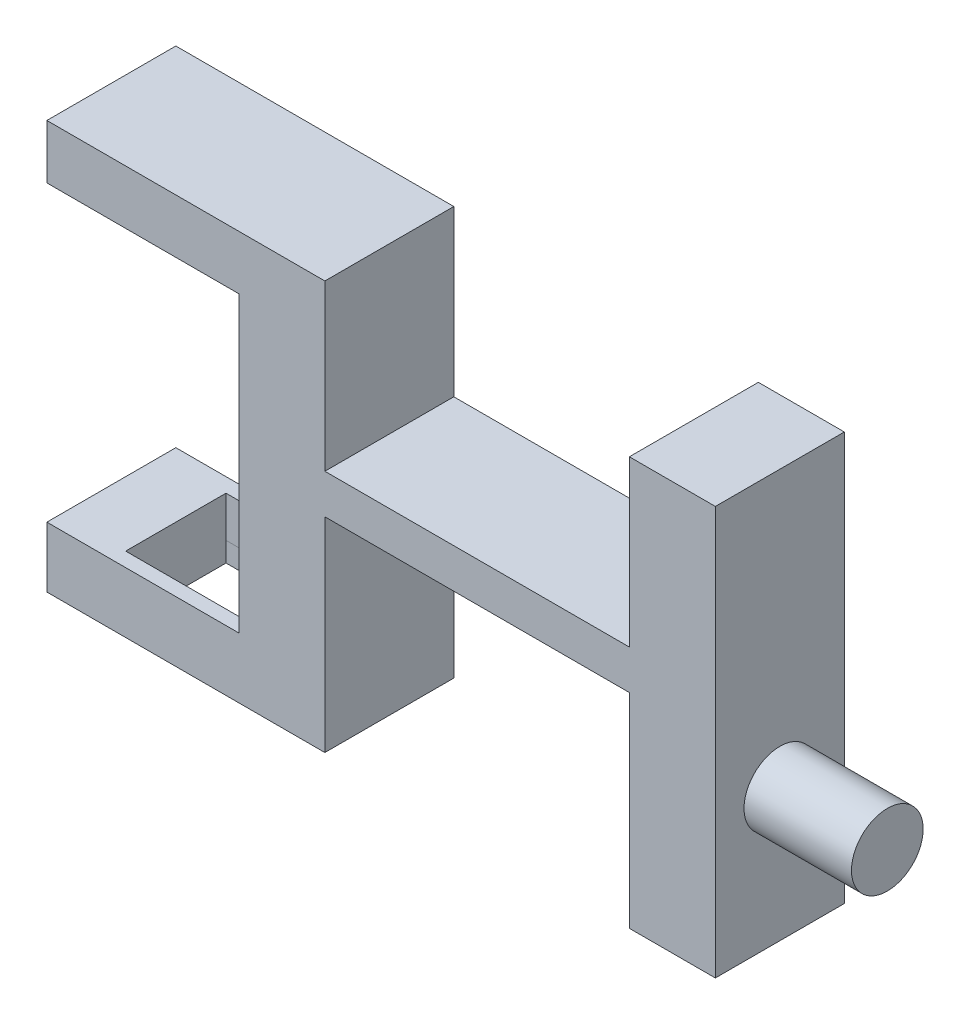
SolidWorks part; units mm, degrees
material "PLA"
ref_plane "Front Plane" through (0, 0, 0) normal (0, 0, 1) x (1, 0, 0)
ref_plane "Top Plane" through (0, 0, 0) normal (0, 1, 0) x (1, 0, 0)
ref_plane "Right Plane" through (0, 0, 0) normal (1, 0, 0) x (0, 0, -1)
sketch "Sketch2" plane through (0, 0, 0) normal (0, 0, 1) x (1, 0, 0)
  line L0 (0, -55) -> (0, 55) construction
  line L1 (0, 55) -> (66.5, 55)
  line L2 (0, 55) -> (0, 0)
  line L3 (0, 0) -> (66.5, 0)
  line L4 (66.5, 55) -> (66.5, 0)
  line L5 (55, 0) -> (-55, 0) construction
  line L7 (12, 50.75) -> (54.5, 50.75)
  line L8 (12, 50.75) -> (12, 30.25)
  line L9 (12, 30.25) -> (54.5, 30.25)
  line L10 (54.5, 50.75) -> (54.5, 30.25)
  line L11 (12, 24.75) -> (54.5, 24.75)
  line L12 (12, 24.75) -> (12, 4.25)
  line L13 (12, 4.25) -> (54.5, 4.25)
  line L14 (54.5, 24.75) -> (54.5, 4.25)
  dimension "D1" = 55
  dimension "D2" = 12
  dimension "D3" = 42.5
  dimension "D4" = 20.5
  dimension "D5" = 5.5
  dimension "D6" = 42.5
  dimension "D7" = 20.5
  dimension "D8" = 12
  dimension "D9" = 4.25
  dimension "D10" = 12
extrude "Boss-Extrude1" add sketch "Sketch2" along normal blind 18
sketch "Sketch3" plane through (0, 0, 18) normal (0, 0, 1) x (1, 0, 0)
  line L2 (12, 24.75) -> (12, 4.25) construction
  line L3 (54.5, 24.75) -> (12, 24.75) construction
  circle A8 centre (8.15, 19.75) radius 2.5
  circle A9 centre (8.15, 9.75) radius 2.5
  circle A10 centre (57.85, 9.75) radius 2.5
  circle A11 centre (57.85, 19.75) radius 2.5
  dimension "D9" = 45.85
  dimension "D10" = 45.85
  dimension "D11" = 5
  dimension "D12" = 5
  dimension "D13" = 3.85
  dimension "D14" = 3.85
  dimension "D15" = 10
  dimension "D16" = 5
  dimension "D17" = 5
  dimension "D18" = 5
  dimension "D19" = 5
  dimension "D24" = 10
sketch "Sketch5" plane through (0, 0, 0) normal (-1, 0, 0) x (0, 0, 1)
  line L0 (0, -55) -> (0, 55) construction
  line L1 (0, 55) -> (2, 55)
  line L2 (0, 55) -> (0, 49)
  line L3 (0, 49) -> (2, 49)
  line L4 (2, 55) -> (2, 49)
  line L5 (18, 55) -> (0, 55) construction
  line L6 (55, 0) -> (-55, 0) construction
  line L7 (18, 55) -> (16, 55)
  line L8 (18, 55) -> (18, 49)
  line L9 (18, 49) -> (16, 49)
  line L10 (16, 55) -> (16, 49)
  line L11 (0, 0) -> (2, 0)
  line L12 (0, 0) -> (0, 6)
  line L13 (0, 6) -> (2, 6)
  line L14 (2, 0) -> (2, 6)
  line L15 (18, 0) -> (16, 0)
  line L16 (18, 0) -> (18, 6)
  line L17 (18, 6) -> (16, 6)
  line L18 (16, 0) -> (16, 6)
  line L19 (18, 55) -> (18, 0) construction
  dimension "D1" = 2
  dimension "D2" = 2
  dimension "D3" = 6
  dimension "D4" = 6
  dimension "D5" = 2
  dimension "D6" = 2
  dimension "D7" = 6
  dimension "D8" = 6
extrude "Boss-Extrude2" add sketch "Sketch5" along normal blind 26.8
sketch "Sketch6" plane through (0, 0, 2) normal (0, 0, 1) x (1, 0, 0)
  line L0 (-26.8, 49) -> (0, 49) construction
  line L1 (-23.8, 49) -> (-26.8, 49)
  line L2 (-23.8, 49) -> (-23.8, 55)
  line L3 (-23.8, 55) -> (-26.8, 55)
  line L4 (-26.8, 49) -> (-26.8, 55)
  line L5 (66.5, 55) -> (-26.8, 55) construction
  line L6 (-26.8, 55) -> (-26.8, 49) construction
  line L7 (55, 0) -> (-55, 0) construction
  line L8 (-26.8, 6) -> (-24.8, 6)
  line L9 (-26.8, 6) -> (-26.8, 0)
  line L10 (-26.8, 0) -> (-24.8, 0)
  line L11 (-24.8, 6) -> (-24.8, 0)
  dimension "D1" = 3
  dimension "D2" = 2
extrude "Boss-Extrude3" add sketch "Sketch6" along normal up to next
sketch "Sketch8" plane through (0, 0, 18) normal (0, 0, 1) x (1, 0, 0)
  line L0 (66.5, 55) -> (-26.8, 55) construction
  line L1 (12, 50.75) -> (54, 50.75)
  line L2 (12, 50.75) -> (12, 55)
  line L3 (12, 55) -> (54, 55)
  line L4 (54, 50.75) -> (54, 55)
  line L5 (55, 0) -> (-55, 0) construction
  line L6 (12, 4.25) -> (54.5, 4.25)
  line L7 (12, 4.25) -> (12, 0)
  line L8 (12, 0) -> (54.5, 0)
  line L9 (54.5, 4.25) -> (54.5, 0)
extrude "Cut-Extrude3" cut sketch "Sketch8" against normal up to next
sketch "Sketch12" plane through (0, 0, 2) normal (0, 0, 1) x (1, 0, 0)
  line L0 (-26.8, 6) -> (0, 6) construction
  line L1 (-8, 6) -> (-5, 6)
  line L2 (-8, 6) -> (-8, 0)
  line L3 (-8, 0) -> (-5, 0)
  line L4 (-5, 6) -> (-5, 0)
  line L5 (55, 0) -> (-55, 0) construction
  line L6 (0, -55) -> (0, 55) construction
  dimension "D1" = 3
  dimension "D2" = 5
extrude "Boss-Extrude7" add sketch "Sketch12" along normal up to surface (14 mm away) up to face at (-12.4, 3, 16)
sketch "Sketch14" plane through (-8, 0, 0) normal (-1, 0, 0) x (0, 0, 1)
  line L0 (18, 6) -> (0, 6) construction
  line L1 (7, 6) -> (11, 6)
  line L2 (7, 6) -> (7, 0)
  line L3 (7, 0) -> (11, 0)
  line L4 (11, 6) -> (11, 0)
  line L5 (55, 0) -> (-55, 0) construction
  line L6 (0, -55) -> (0, 55) construction
  line L7 (18, 0) -> (18, 6) construction
  dimension "D1" = 7
  dimension "D2" = 7
extrude "Boss-Extrude8" add sketch "Sketch14" along normal up to surface (16.8 mm away) up to face at (-24.8, 3, 9)
sketch "Sketch17" plane through (0, 0, 2) normal (0, 0, 1) x (1, 0, 0)
  line L1 (-23.8, 55) -> (0, 55)
  line L2 (-23.8, 55) -> (-23.8, 49)
  line L3 (-23.8, 49) -> (0, 49)
  line L4 (0, 55) -> (0, 49)
extrude "Boss-Extrude9" add sketch "Sketch17" along normal blind 14 and the other way blind 1
sketch "Sketch18" plane through (0, 6, 0) normal (0, 1, 0) x (1, 0, 0)
  line L1 (-5, -2) -> (-24.8, -2)
  line L2 (-5, -2) -> (-5, -16)
  line L3 (-5, -16) -> (-24.8, -16)
  line L4 (-24.8, -2) -> (-24.8, -16)
extrude "Cut-Extrude4" cut sketch "Sketch18" against normal blind 10
sketch "Sketch20" plane through (0, 6, 0) normal (0, 1, 0) x (1, 0, 0)
  line L0 (-24.8, -16) -> (0, -16) construction
  line L1 (-24.8, -2) -> (-19.8, -2)
  line L2 (-24.8, -2) -> (-24.8, -16)
  line L3 (-24.8, -16) -> (-19.8, -16)
  line L4 (-19.8, -2) -> (-19.8, -16)
  dimension "D1" = 5
extrude "Boss-Extrude10" add sketch "Sketch20" against normal blind 6
sketch "Sketch22" plane through (0, 55, 0) normal (0, 1, 0) x (1, 0, 0)
  line L0 (-55, 0) -> (55, 0) construction
  line L1 (-26.8, -18) -> (12, -18)
  line L2 (-26.8, -18) -> (-26.8, 0)
  line L3 (-26.8, 0) -> (12, 0)
  line L4 (12, -18) -> (12, 0)
  line L5 (12, -18) -> (12, 0) construction
extrude "Boss-Extrude11" add sketch "Sketch22" along normal blind 1
sketch "Sketch23" plane through (0, 49, 0) normal (0, -1, 0) x (1, 0, 0)
  line L1 (0, 18) -> (-26.8, 18)
  line L2 (0, 18) -> (0, 0)
  line L3 (0, 0) -> (-26.8, 0)
  line L4 (-26.8, 18) -> (-26.8, 0)
extrude "Boss-Extrude12" add sketch "Sketch23" along normal blind 1
sketch "Sketch24" plane through (0, 6, 0) normal (0, 1, 0) x (1, 0, 0)
  line L0 (0, 0) -> (-26.8, 0)
  line L1 (-26.8, 0) -> (-26.8, -18)
  line L2 (-26.8, -18) -> (0, -18)
  line L3 (0, -18) -> (0, -16)
  line L4 (0, -16) -> (-19.8, -16)
  line L5 (-19.8, -16) -> (-19.8, -2)
  line L6 (-19.8, -2) -> (0, -2)
  line L7 (0, -2) -> (0, 0)
extrude "Boss-Extrude13" add sketch "Sketch24" along normal blind 1
sketch "Sketch25" plane through (0, 55, 0) normal (0, 1, 0) x (1, 0, 0)
  line L0 (-55, 0) -> (55, 0) construction
  line L1 (66.5, -18) -> (54.5, -18)
  line L2 (66.5, -18) -> (66.5, 0)
  line L3 (66.5, 0) -> (54.5, 0)
  line L4 (54.5, -18) -> (54.5, 0)
  line L5 (54.5, -18) -> (54.5, 0) construction
extrude "Boss-Extrude14" add sketch "Sketch25" along normal blind 1
sketch "Sketch27" plane through (0, 0, 0) normal (0, -1, 0) x (1, 0, 0)
  line L0 (-26.8, 18) -> (12, 18)
  line L1 (12, 18) -> (12, 0)
  line L2 (55, 0) -> (-55, 0) construction
  line L3 (12, 18) -> (12, 0) construction
  line L4 (12, 0) -> (-26.8, 0)
  line L5 (-26.8, 0) -> (-26.8, 18) construction
  line L6 (-26.8, 0) -> (-26.8, 18)
  line L7 (-19.8, 16) -> (-19.8, 2)
  line L8 (-19.8, 2) -> (0, 2)
  line L9 (0, 2) -> (0, 16)
  line L10 (0, 16) -> (0, 2) construction
  line L11 (-19.8, 16) -> (0, 16) construction
  line L12 (0, 16) -> (-19.8, 16)
extrude "Boss-Extrude15" add sketch "Sketch27" along normal blind 1
sketch "Sketch28" plane through (0, 0, 0) normal (0, -1, 0) x (1, 0, 0)
  line L0 (55, 0) -> (-55, 0) construction
  line L1 (54.5, 18) -> (66.5, 18)
  line L2 (54.5, 18) -> (54.5, 0)
  line L3 (54.5, 0) -> (66.5, 0)
  line L4 (66.5, 18) -> (66.5, 0)
  line L5 (66.5, 18) -> (66.5, 0) construction
extrude "Boss-Extrude16" add sketch "Sketch28" along normal blind 1
sketch "Sketch32" plane through (-26.8, 0, 0) normal (-1, 0, 0) x (0, 0, 1)
  line L0 (0, -55) -> (0, 55) construction
  line L1 (18, 7) -> (0, 7)
  line L2 (18, 7) -> (18, 4.25)
  line L3 (18, 4.25) -> (0, 4.25)
  line L4 (0, 7) -> (0, 4.25)
  dimension "D1" = 2.75
extrude "Cut-Extrude8" cut sketch "Sketch32" against normal blind 26.8
sketch "Sketch33" plane through (0, -1, 0) normal (0, -1, 0) x (1, 0, 0)
  line L0 (-26.8, 18) -> (12, 18)
  line L1 (12, 18) -> (12, 0)
  line L2 (55, 0) -> (-55, 0) construction
  line L3 (12, 18) -> (12, 0) construction
  line L4 (12, 0) -> (-26.8, 0)
  line L5 (-26.8, 18) -> (-26.8, 0) construction
  line L6 (-26.8, 0) -> (-26.8, 18)
  line L7 (-19.8, 16) -> (0, 16)
  line L8 (0, -55) -> (0, 55) construction
  line L9 (0, 16) -> (-19.8, 16) construction
  line L10 (0, 16) -> (0, 1.9658)
  line L11 (0, 1.9658) -> (-19.8, 2)
  line L12 (-19.8, 2) -> (-19.8, 16)
extrude "Boss-Extrude17" add sketch "Sketch33" along normal blind 2.75
sketch "Sketch34" plane through (0, -1, 0) normal (0, -1, 0) x (1, 0, 0)
  line L0 (31.9, 0) -> (-31.9, 0) construction
  line L1 (54.5, 18) -> (66.5, 18)
  line L2 (54.5, 18) -> (54.5, 0)
  line L3 (54.5, 0) -> (66.5, 0)
  line L4 (66.5, 18) -> (66.5, 0)
  line L5 (66.5, 0) -> (66.5, 18) construction
extrude "Boss-Extrude18" add sketch "Sketch34" along normal blind 2.75
sketch "Sketch35" plane through (0, 48, 0) normal (0, -1, 0) x (1, 0, 0)
  line L1 (-26.8, 18) -> (0, 18)
  line L2 (-26.8, 18) -> (-26.8, 0)
  line L3 (-26.8, 0) -> (0, 0)
  line L4 (0, 18) -> (0, 0)
extrude "Boss-Extrude19" add sketch "Sketch35" along normal blind 2.3
sketch "Sketch36" plane through (0, 56, 0) normal (0, 1, 0) x (1, 0, 0)
  line L0 (-32.8625, 0) -> (32.8625, 0) construction
  line L1 (66.5, -18) -> (54.5, -18)
  line L2 (66.5, -18) -> (66.5, 0)
  line L3 (66.5, 0) -> (54.5, 0)
  line L4 (54.5, -18) -> (54.5, 0)
  line L5 (54.5, -18) -> (54.5, 0) construction
  line L7 (12, -18) -> (-26.8, -18)
  line L8 (12, -18) -> (12, 0)
  line L9 (12, 0) -> (-26.8, 0)
  line L10 (-26.8, -18) -> (-26.8, 0)
extrude "Cut-Extrude9" cut sketch "Sketch36" against normal blind 2.75
sketch "Sketch37" plane through (-26.8, 0, 0) normal (-1, 0, 0) x (0, 0, 1)
  line L0 (0, 53.25) -> (18, 53.25) construction
  line L1 (0, -32.8625) -> (0, 32.8625) construction
  line L2 (18, 45.7) -> (18, 53.25) construction
  circle A0 centre (4, 49.45) radius 2.5
  circle A1 centre (14, 49.45) radius 2.5
  dimension "D1" = 3.8
  dimension "D2" = 4
  dimension "D3" = 4
  dimension "D4" = 3.8
  dimension "D5" = 5
  dimension "D6" = 5
sketch "Sketch38" plane through (-26.8, 0, 0) normal (-1, 0, 0) x (0, 0, 1)
  line L0 (0, 4.25) -> (18, 4.25) construction
  line L1 (0, -32.8625) -> (0, 32.8625) construction
  line L2 (18, -3.75) -> (18, 4.25) construction
  circle A0 centre (4, 0.45) radius 2.5
  circle A1 centre (14, 0.45) radius 2.5
  dimension "D1" = 3.8
  dimension "D2" = 5
  dimension "D3" = 4
  dimension "D4" = 5
  dimension "D5" = 4
  dimension "D6" = 3.8
extrude "Cut-Extrude10" cut sketch "Sketch37" against normal blind 6
sketch "Sketch39" plane through (0, 0, 0) normal (0, 0, -1) x (-1, 0, 0)
  line L0 (-54.5, 30.25) -> (-54.5, 27.5) construction
  line L2 (-54.5, 27.5) -> (-66.5, 27.5) construction
  line L3 (-66.5, -3.75) -> (-66.5, 53.25) construction
  circle A2 centre (-8.15, 19.75) radius 2.5
  circle A3 centre (-8.15, 9.75) radius 2.5
  circle A6 centre (-57.85, 19.75) radius 2.5
  circle A7 centre (-57.85, 9.75) radius 2.5
  circle A8 centre (-8.15, 45.25) radius 2.5
  circle A9 centre (-8.15, 35.25) radius 2.5
  circle A10 centre (-57.85, 45.25) radius 2.5
  circle A11 centre (-57.85, 35.25) radius 2.5
  dimension "D1" = 2.75
  dimension "D4" = 5
  dimension "D5" = 5
  dimension "D6" = 5
  dimension "D7" = 5
extrude "Cut-Extrude12" cut sketch "Sketch39" against normal blind 10
extrude "Cut-Extrude11" cut sketch "Sketch38" against normal blind 6
sketch "Sketch40" plane through (0, 0, 0) normal (0, 0, -1) x (-1, 0, 0)
  line L0 (-57.85, 35.25) -> (-8.15, 35.25) construction
  line L1 (-57.85, 19.75) -> (-8.15, 19.75) construction
  line L3 (-54, 50.75) -> (-54.5, 50.75)
  line L4 (-54, 50.75) -> (-54, 55)
  line L5 (-54, 55) -> (-54.5, 55)
  line L6 (-54.5, 50.75) -> (-54.5, 55)
extrude "Cut-Extrude13" cut sketch "Sketch40" against normal up to surface (18 mm away) up to face at (25.44, 30.97, 18)
sketch "Sketch43" plane through (0, 4.25, 0) normal (0, 1, 0) x (1, 0, 0)
  line L0 (0, 0) -> (-26.8, 0)
  line L1 (-26.8, 0) -> (-26.8, -18)
  line L2 (-26.8, -18) -> (0, -18)
  line L3 (0, -18) -> (0, -16)
  line L4 (0, -16) -> (-19.8, -16)
  line L5 (-19.8, -16) -> (-19.8, -2)
  line L6 (-19.8, -2) -> (0, -2)
  line L7 (0, -2) -> (0, 0)
extrude "Boss-Extrude21" add sketch "Sketch43" along normal blind 0.45
sketch "Sketch44" plane through (66.5, 0, 0) normal (1, 0, 0) x (0, 0, -1)
  line L0 (0, -3.75) -> (-18, -3.75) construction
  line L1 (-18, -3.75) -> (-18, 53.25) construction
  circle A0 centre (-9, 14.75) radius 5
  dimension "D1" = 10
  dimension "D2" = 18.5
  dimension "D3" = 9
extrude "Boss-Extrude22" add sketch "Sketch44" along normal blind 15
sketch "Sketch45" plane through (-19.8, 0, 0) normal (1, 0, 0) x (0, 0, -1)
  line L1 (-16, 4.7) -> (-2, 4.7)
  line L2 (-16, 4.7) -> (-16, -3.75)
  line L3 (-16, -3.75) -> (-2, -3.75)
  line L4 (-2, 4.7) -> (-2, -3.75)
  line L5 (-16, 4.7) -> (-2, -3.75) construction
  line L6 (-16, -3.75) -> (-2, 4.7) construction
  point P4 (-9, 0.475)
extrude "Boss-Extrude23" add sketch "Sketch45" along normal blind 2
